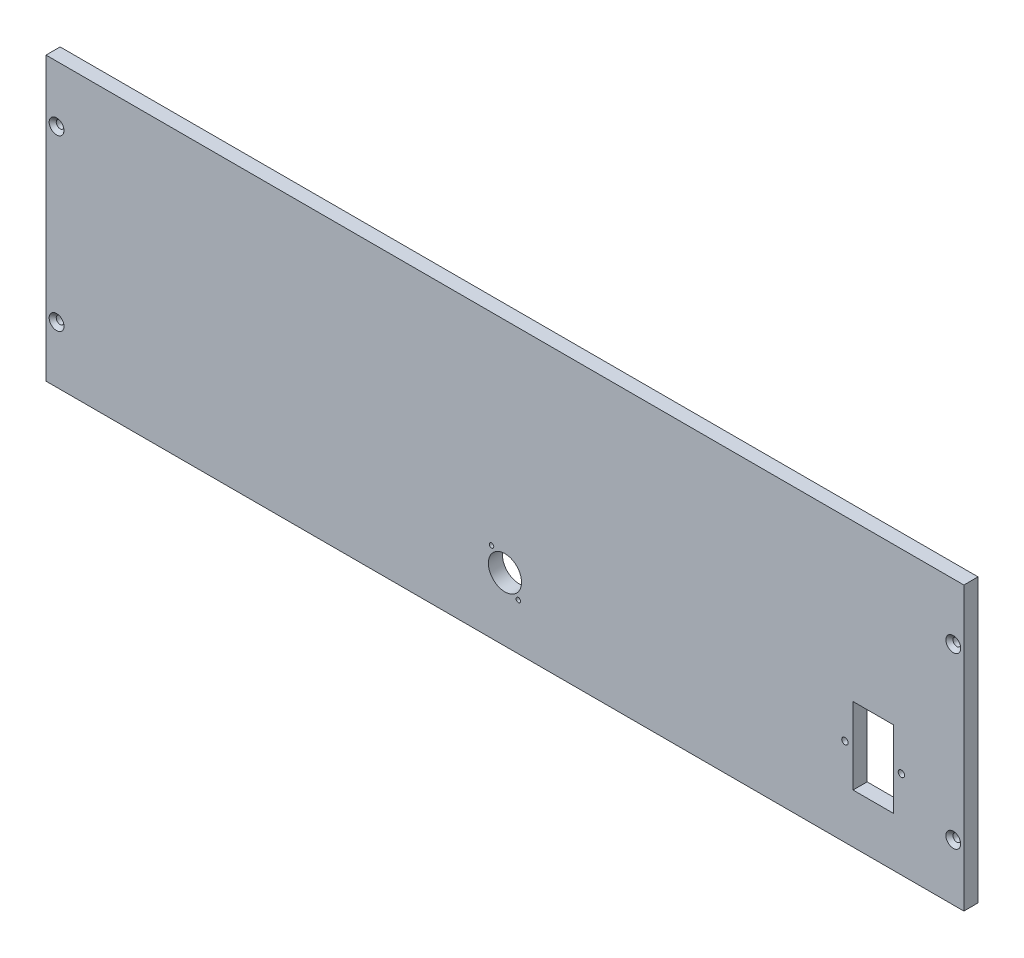
SolidWorks part; units mm, degrees
ref_plane "Plan de face" through (0, 0, 0) normal (0, 0, 1) x (1, 0, 0)
ref_plane "Plan de dessus" through (0, 0, 0) normal (0, 1, 0) x (1, 0, 0)
ref_plane "Plan de droite" through (0, 0, 0) normal (1, 0, 0) x (0, 0, -1)
sketch "Esquisse1" plane through (0, 0, 0) normal (0, 0, 1) x (1, 0, 0)
  line L1 (0, 0) -> (650, 0)
  line L2 (0, 0) -> (0, 200)
  line L3 (0, 200) -> (650, 200)
  line L4 (650, 0) -> (650, 200)
  dimension "D1" = 200
  dimension "D2" = 650
extrude "Boss.-Extru.1" add sketch "Esquisse1" along normal blind 10
sketch "Esquisse2" plane through (0, 0, 10) normal (0, 0, 1) x (1, 0, 0)
  line L0 (0, 200) -> (0, 0) construction
  line L1 (650, 200) -> (0, 200) construction
  line L2 (0, 0) -> (650, 0) construction
  line L3 (650, 0) -> (650, 200) construction
  circle A0 centre (7.5, 160) radius 2.75
  circle A1 centre (642.5, 160) radius 2.75
  circle A2 centre (7.5, 40) radius 2.75
  circle A3 centre (642.5, 40) radius 2.75
  dimension "D1" = 5.5
  dimension "D2" = 5.5
  dimension "D3" = 5.5
  dimension "D4" = 5.5
  dimension "D5" = 7.5
  dimension "D6" = 7.5
  dimension "D7" = 40
  dimension "D8" = 40
  dimension "D9" = 40
  dimension "D10" = 40
  dimension "D11" = 7.5
  dimension "D12" = 7.5
extrude "Enlèv. mat.-Extru.1" cut sketch "Esquisse2" against normal blind 10
chamfer "Chanfrein1" distance 2.5 angle 45 4 edges at (10.25, 160, 10) (10.25, 40, 10) (645.25, 40, 10) (645.25, 160, 10)
sketch "Esquisse3" plane through (0, 0, 10) normal (0, 0, 1) x (1, 0, 0)
  line L0 (0, 0) -> (650, 0) construction
  line L1 (334.5004, 33.0006) -> (325, 45)
  line L2 (325, 45) -> (315.4996, 56.9994)
  line L3 (325, 45) -> (265.8175, 45)
  line L4 (325, 45) -> (364.3682, 45)
  line L5 (650, 0) -> (650, 200) construction
  line L6 (571.5, 35) -> (600, 35)
  line L7 (571.5, 35) -> (571.5, 89.3)
  line L8 (571.5, 89.3) -> (600, 89.3)
  line L9 (600, 35) -> (600, 89.3)
  circle A0 centre (325, 45) radius 11.75
  circle A1 centre (315.4996, 56.9994) radius 1.6
  circle A2 centre (334.5004, 33.0006) radius 1.6
  circle A3 centre (565.75, 62.15) radius 2.25
  circle A4 centre (605.75, 62.15) radius 2.25
  point P4 (325, 0)
  point P19 (585.75, 89.3)
  point P20 (571.5, 62.15)
  dimension "D1" = 23.5
  dimension "D4" = 3.2
  dimension "D5" = 3.2
  dimension "D14" = 4.5
  dimension "D15" = 4.5
  dimension "D2" = 0
  dimension "D3" = 45
  dimension "D6" = 30.61
  dimension "D7" = 15.305
  dimension "D8" = 51.63
  dimension "D9" = 180
  dimension "D10" = 51.63
  dimension "D11" = 15.305
  dimension "D12" = 28.5
  dimension "D13" = 54.3
  dimension "D16" = 40
  dimension "D17" = 20
  dimension "D18" = 0
  dimension "D19" = 35
  dimension "D20" = 50
  dimension "D21" = 20
extrude "Enlèv. mat.-Extru.2" cut sketch "Esquisse3" against normal blind 10 contours L3 A0 L1 | L4 A0 L2 | L1 A0 L4 | L2 A0 L3 | A1 | A2 | L6 L9 L8 L7 | A3 | A4 region at (314.1, 57.6764, 10) region at (322.2589, 39.3335, 10) region at (331.8154, 41.7031, 10) region at (335.1774, 34.4002, 10) region at (318.1846, 48.2969, 10) region at (327.7411, 50.6665, 10) region at (585.75, 62.15, 10)
